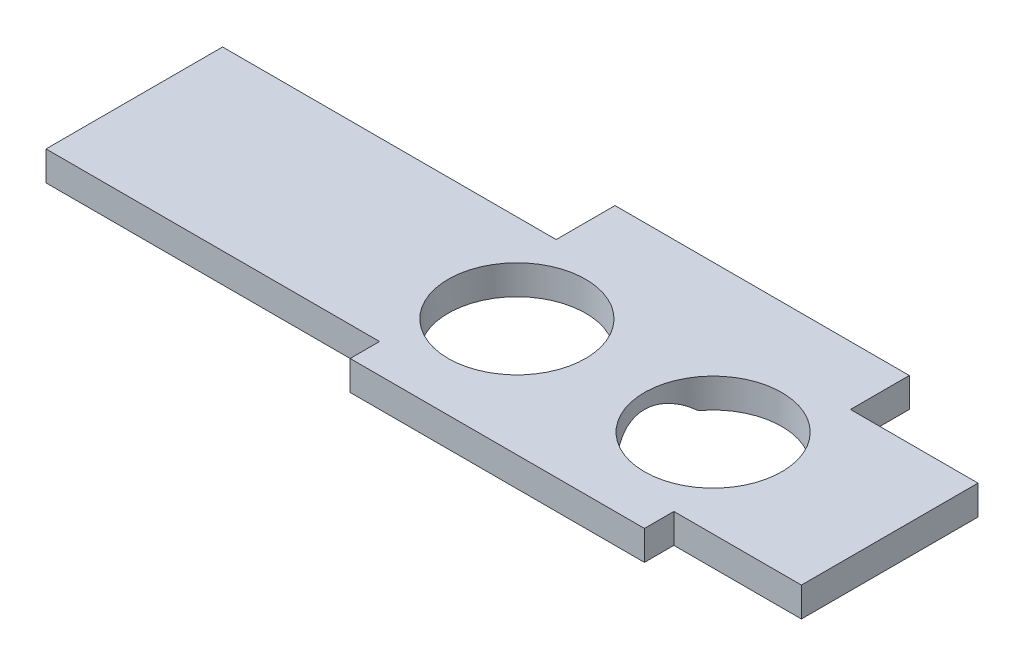
SolidWorks part; units mm, degrees
ref_plane "Front Plane" through (0, 0, 0) normal (0, 0, 1) x (1, 0, 0)
ref_plane "Top Plane" through (0, 0, 0) normal (0, 1, 0) x (1, 0, 0)
ref_plane "Right Plane" through (0, 0, 0) normal (1, 0, 0) x (0, 0, -1)
sketch "Sketch1" plane through (0, 0, 0) normal (0, 1, 0) x (1, 0, 0)
  line L0 (-3, 0) -> (-3, 50000) construction
  line L1 (3, 0) -> (3, 50000) construction
  line L2 (5, 0) -> (5, 50000) construction
  line L3 (-30.5, 9) -> (5.5, 9)
  line L4 (-30.5, 9) -> (-30.5, -9)
  line L5 (-30.5, -9) -> (5.5, -9)
  line L6 (5.5, 9) -> (5.5, -9) construction
  line L7 (-5, 0) -> (-5, 50000) construction
  line L9 (25.5, 9) -> (-10.5, 9)
  line L10 (25.5, 9) -> (25.5, -9)
  line L11 (25.5, -9) -> (-10.5, -9)
  line L12 (-10.5, 9) -> (-10.5, -9) construction
  line L13 (-30.5, 9) -> (25.5, 9)
  line L14 (-30.5, 9) -> (-30.5, -9)
  line L15 (-30.5, -9) -> (25.5, -9)
  line L16 (25.5, 9) -> (25.5, -9)
  circle A0 centre (0, 0) radius 3 construction
  circle A1 centre (-12.5, 0) radius 7
  circle A2 centre (7.5, 0) radius 7
  circle A3 centre (-10, 0) radius 15 construction
  circle A4 centre (10, 0) radius 15 construction
  point P11 (-30.5, 0)
  point P18 (-12.5, 9)
  point P25 (9.3539, 9)
  point P26 (7.5, 9)
  point P28 (25.5, 0)
  dimension "D1" = 6
  dimension "D2" = 36
  dimension "D5" = 14
  dimension "D6" = 14
  dimension "D9" = 2
  dimension "D7" = 2
  dimension "D8" = 7
  dimension "D10" = 12.5
  dimension "D3" = 7
  dimension "D4" = 18
  dimension "D11" = 7.5
  dimension "D12" = 36
extrude "BaseShape" add sketch "Sketch1" along normal blind 3 contours A2 | L14 L13 L16 L15 | A1 region at (7.5, 0, 0)
sketch "Sketch2" plane through (0, 0, 0) normal (0, -1, 0) x (1, 0, 0)
  line L0 (-30.5, -9) -> (25.5, -9) construction
  line L1 (-30.5, -9) -> (-51.5, -9)
  line L2 (-30.5, -9) -> (-30.5, 9)
  line L3 (-30.5, 9) -> (-51.5, 9)
  line L4 (-51.5, -9) -> (-51.5, 9)
  line L5 (-17.5, -9) -> (12.5, -9)
  line L6 (-17.5, -9) -> (-17.5, -15)
  line L7 (-17.5, -15) -> (12.5, -15)
  line L8 (12.5, -9) -> (12.5, -15)
  line L9 (-30.5, -9) -> (-17.5, -9) construction
  line L10 (12.5, -9) -> (25.5, -9) construction
  line L11 (-17.5, 9) -> (-17.5, 12)
  line L12 (-30.5, 9) -> (25.5, 9) construction
  line L13 (-17.5, 12) -> (12.5, 12)
  line L14 (12.5, 12) -> (12.5, 9)
  line L15 (12.5, 9) -> (-17.5, 9)
  dimension "D1" = 21
  dimension "D2" = 6
  dimension "D3" = 30
  dimension "D4" = 3
extrude "FingerJoints" add sketch "Sketch2" against normal up to surface (3 mm away) up to face at (-2.5, 3, 0)
ref_plane "Plane1" through (-5.5, 0, 0) normal (-1, 0, 0) x (0, 0, 1)
sketch "Sketch4" plane through (-5.5, 0, 0) normal (-1, 0, 0) x (0, 0, 1)
  line L0 (-4.1533, 0) -> (4.1533, 0)
  line L2 (0, 2.0241) -> (0, 50002.0241) construction
  arc A1 (4.1533, 0) -> (-4.1533, 0) centre (0, -5) ccw
  dimension "D1" = 13
  dimension "D2" = 5
extrude "Cut-Extrude1" cut sketch "Sketch4" against normal blind 10 from offset 2
